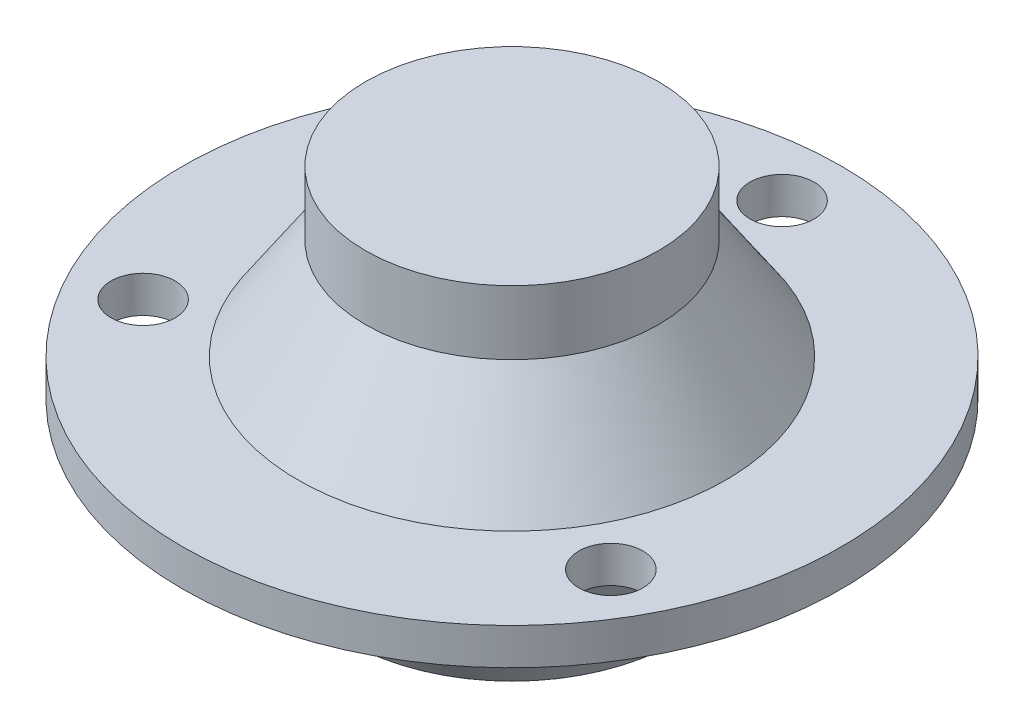
SolidWorks part; units mm, degrees
ref_plane "Plan de face" through (0, 0, 0) normal (0, 0, 1) x (1, 0, 0)
ref_plane "Plan de dessus" through (0, 0, 0) normal (0, 1, 0) x (1, 0, 0)
ref_plane "Plan de droite" through (0, 0, 0) normal (1, 0, 0) x (0, 0, -1)
sketch "Esquisse1" plane through (0, 0, 0) normal (0, 0, 1) x (1, 0, 0)
  line L0 (0, 0) -> (0, 9)
  line L1 (0, 9) -> (8, 9)
  line L3 (11.69, 0) -> (18, 0)
  line L4 (18, 0) -> (18, -2)
  line L5 (18, -2) -> (12.5, -2)
  line L6 (12.5, -2) -> (9, -9)
  line L7 (9, -9) -> (0, -9)
  line L8 (0, -9) -> (0, 0)
  line L9 (8, 9) -> (8, 5.5)
  line L10 (8, 5.5) -> (11.69, 0)
  line L11 (0, 2.8) -> (9.8115, 2.8) construction
  dimension "D1" = 11.69
  dimension "D2" = 18
  dimension "D3" = 8
  dimension "D4" = 12.5
  dimension "D5" = 9
  dimension "D6" = 2
  dimension "D7" = 3.5
  dimension "D8" = 9
  dimension "D9" = 7
  dimension "D10" = 6.2
  dimension "D11" = 9.8115
revolve "Révolution1" add sketch "Esquisse1" angle 360 about L0
sketch "Esquisse2" plane through (0, 0, 0) normal (0, 0, 1) x (1, 0, 0)
  line L0 (0, 7) -> (0, -13)
  line L1 (8, 9) -> (-8, 9) construction
  line L2 (-9, -9) -> (9, -9) construction
  arc A0 (0, -13) -> (0, 7) centre (0, -3) ccw
  point P4 (8, -9)
  point P8 (0, 0)
  dimension "D1" = 22
  dimension "D2" = 1
revolve "Révolution2" add sketch "Esquisse2" angle 360 about L0
sketch "Esquisse3" plane through (0, 0, 0) normal (0, 1, 0) x (1, 0, 0)
  circle A0 centre (0, 14.75) radius 1.75
  circle A1 centre (0, 0) radius 18 construction
  point P2 (0, 13)
  point P5 (0, -18)
  point P6 (-0.2195, 15.2156)
  point P7 (0, 0)
  point P9 (0, 0)
  dimension "D1" = 3.5
  dimension "D2" = 31
extrude "Enlèv. mat.-Extru.1" cut sketch "Esquisse3" against normal through all
ref_axis "Axe1" through (0, -14.1, 0) along (0, 1, 0)
pattern_circular "Répétition circulaire1" count 3 over 360 about axis through (0, -14.1, 0) along (0, 1, 0) of "Enlèv. mat.-Extru.1"
